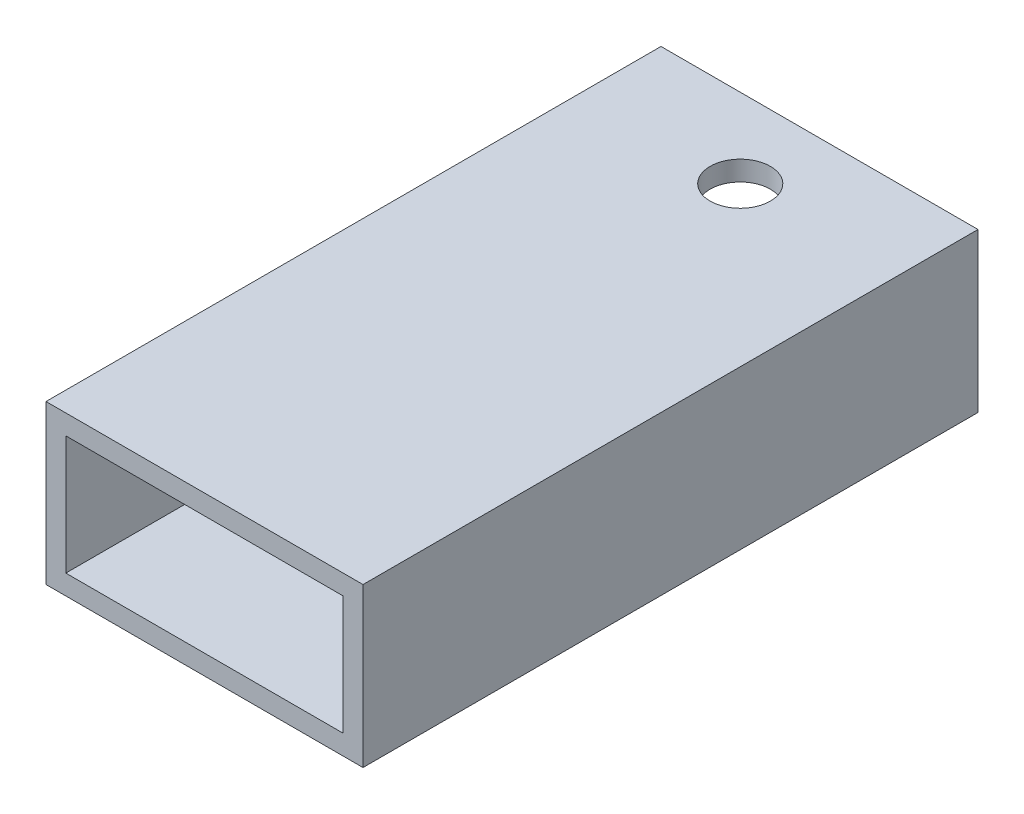
SolidWorks part; units mm, degrees
ref_plane "Front Plane" through (0, 0, 0) normal (0, 0, 1) x (1, 0, 0)
ref_plane "Top Plane" through (0, 0, 0) normal (0, 1, 0) x (1, 0, 0)
ref_plane "Right Plane" through (0, 0, 0) normal (1, 0, 0) x (0, 0, -1)
sketch "Sketch1" plane through (0, 0, 0) normal (0, 0, 1) x (1, 0, 0)
  line L0 (3.175, 3.175) -> (47.625, 3.175)
  line L1 (0, 0) -> (50.8, 0)
  line L2 (0, 0) -> (0, 25.4)
  line L3 (0, 25.4) -> (50.8, 25.4)
  line L4 (50.8, 0) -> (50.8, 25.4)
  line L5 (47.625, 3.175) -> (47.625, 22.225)
  line L6 (3.175, 22.225) -> (47.625, 22.225)
  line L7 (3.175, 3.175) -> (3.175, 22.225)
  dimension "D1" = 50.8
  dimension "D2" = 25.4
  dimension "D3" = 3.175
extrude "Boss-Extrude1" add sketch "Sketch1" along normal blind 98.552
sketch "Sketch2" plane through (0, 0, 0) normal (0, -1, 0) x (1, 0, 0)
  line L0 (0, 0) -> (50.8, 0) construction
  line L1 (50.8, 98.552) -> (50.8, 0) construction
  circle A0 centre (25.4, 12.7) radius 4.826
  point P2 (25.4, 0)
  dimension "D1" = 9.652
  dimension "D2" = 12.7
  dimension "D3" = 25.4
extrude "Cut-Extrude1" cut sketch "Sketch2" against normal through all
